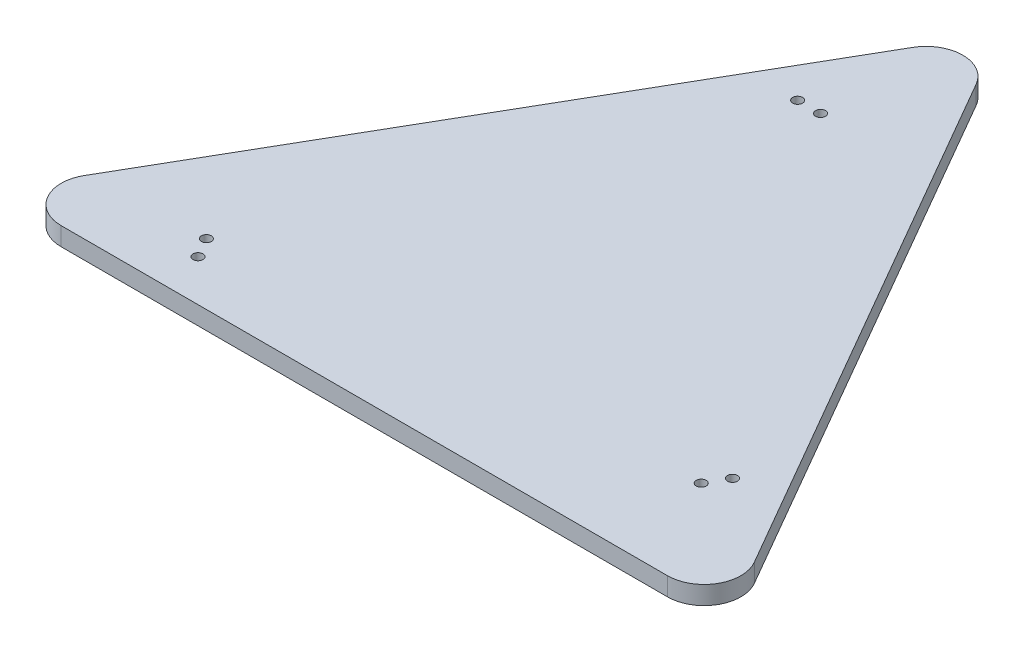
SolidWorks part; units mm, degrees
ref_plane "Front Plane" through (0, 0, 0) normal (0, 0, 1) x (1, 0, 0)
ref_plane "Top Plane" through (0, 0, 0) normal (0, 1, 0) x (1, 0, 0)
ref_plane "Right Plane" through (0, 0, 0) normal (1, 0, 0) x (0, 0, -1)
sketch "Sketch1" plane through (0, 0, 0) normal (0, 1, 0) x (1, 0, 0)
  line L1 (0, 146.647) -> (-127, -73.3235)
  line L2 (-127, -73.3235) -> (127, -73.3235)
  line L3 (127, -73.3235) -> (0, 146.647)
  circle A0 centre (0, 0) radius 73.3235 construction
  dimension "D1" = 254
extrude "Boss-Extrude1" add sketch "Sketch1" along normal blind 6.35
sketch "Sketch2" plane through (0, 6.35, 0) normal (0, 1, 0) x (1, 0, 0)
  line L0 (-127, -73.3235) -> (63.5, 36.6617) construction
  line L1 (127, -73.3235) -> (0, 146.647) construction
  line L2 (0, -73.3235) -> (0, 146.647) construction
  line L3 (-127, -73.3235) -> (127, -73.3235) construction
  line L5 (-63.5, 36.6617) -> (127, -73.3235) construction
  line L7 (0, 146.647) -> (-127, -73.3235) construction
  line L9 (0, -174.0988) -> (150.774, 87.0494)
  line L11 (150.774, 87.0494) -> (-150.774, 87.0494)
  line L12 (-150.774, 87.0494) -> (0, -174.0988)
  circle A0 centre (0, 0) radius 87.0494 construction
  line B0 (88.4014, -30.508) -> (79.5114, -45.9059) construction
  line B1 (84.277, -28.1268) -> (92.5259, -32.8893)
  line B2 (84.277, -28.1268) -> (75.387, -43.5247)
  line B3 (75.387, -43.5247) -> (83.6359, -48.2872)
  line B4 (92.5259, -32.8893) -> (83.6359, -48.2872)
  circle B5 centre (83.0801, -39.7248) radius 1.7272
  circle B6 centre (87.0425, -32.8617) radius 1.7272
  line B7 (-70.6214, -61.3039) -> (-79.5114, -45.9059) construction
  line B8 (-66.497, -58.9226) -> (-74.7459, -63.6851)
  line B9 (-66.497, -58.9226) -> (-75.387, -43.5247)
  line B10 (-75.387, -43.5247) -> (-83.6359, -48.2872)
  line B11 (-74.7459, -63.6851) -> (-83.6359, -48.2872)
  circle B12 centre (-75.9427, -52.0871) radius 1.7272
  circle B13 centre (-71.9803, -58.9502) radius 1.7272
  line B14 (-17.78, 91.8119) -> (0, 91.8119) construction
  line B15 (-17.78, 87.0494) -> (-17.78, 96.5744)
  line B16 (-17.78, 87.0494) -> (0, 87.0494)
  line B17 (0, 87.0494) -> (0, 96.5744)
  line B18 (-17.78, 96.5744) -> (0, 96.5744)
  circle B19 centre (-7.1374, 91.8119) radius 1.7272
  circle B20 centre (-15.0622, 91.8119) radius 1.7272
sketch_block_instance "Block1-4"
sketch_block "Block1" parameters "D3"=3.4544, "D1"=17.78, "D2"=9.525, "D4"=7.1374, "D5"=7.9248
sketch_block_instance "Block1-5"
sketch_block_instance "Block1-6"
extrude "Cut-Extrude1" cut sketch "Sketch2" against normal through all contours B12 | B13 | B5 | B20 | B19 | B6 region at (83.0801, 6.35, 39.7248) region at (-75.9427, 6.35, 52.0871) region at (-71.9803, 6.35, 58.9502) region at (-7.1374, 6.35, -91.8119) region at (-15.0622, 6.35, -91.8119)
fillet "Fillet1" radius 12.7 3 edges at (127, 3.175, 73.3235) (-127, 3.175, 73.3235) (0, 3.175, -146.647)
